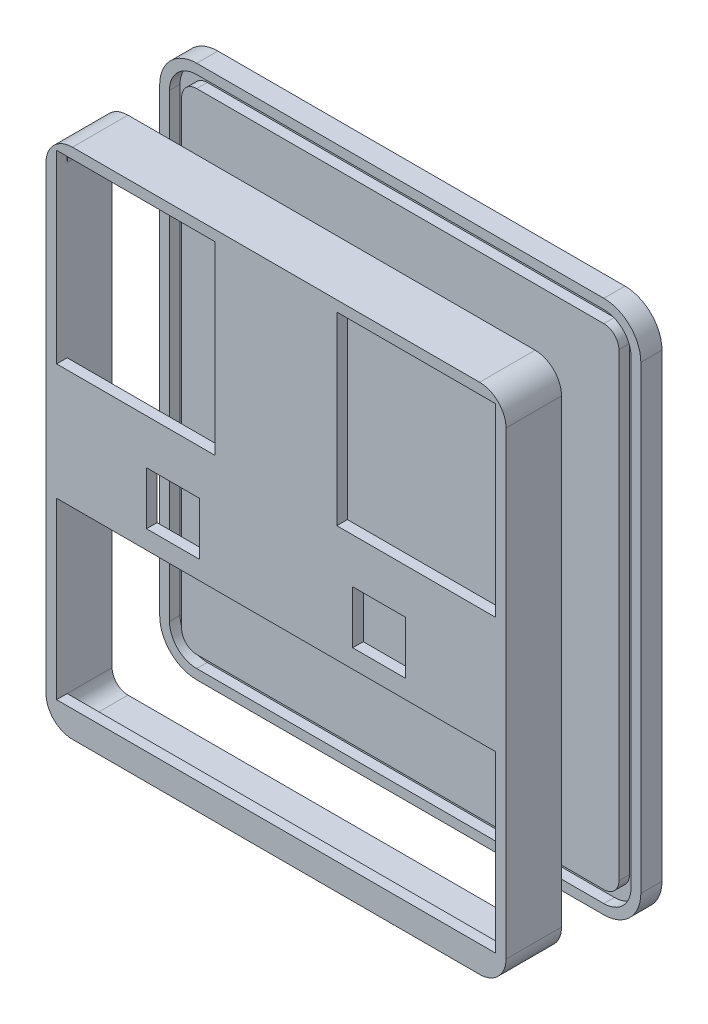
SolidWorks part; units mm, degrees
ref_plane "Front Plane" through (0, 0, 0) normal (0, 0, 1) x (1, 0, 0)
ref_plane "Top Plane" through (0, 0, 0) normal (0, 1, 0) x (1, 0, 0)
ref_plane "Right Plane" through (0, 0, 0) normal (1, 0, 0) x (0, 0, -1)
sketch "Sketch1" plane through (0, 0, 0) normal (0, 0, 1) x (1, 0, 0)
  line L1 (-43.5, -48.5) -> (43.5, -48.5)
  line L2 (-43.5, -48.5) -> (-43.5, 48.5)
  line L3 (-43.5, 48.5) -> (43.5, 48.5)
  line L4 (43.5, -48.5) -> (43.5, 48.5)
  line L5 (-43.5, -48.5) -> (43.5, 48.5) construction
  line L6 (-43.5, 48.5) -> (43.5, -48.5) construction
  point P0 (0, 0)
  dimension "D1" = 87
  dimension "D2" = 97
extrude "Boss-Extrude1" add sketch "Sketch1" along normal blind 8.5
fillet "Fillet1" radius 5 4 edges at (43.5, -48.5, 4.25) (-43.5, -48.5, 4.25) (-43.5, 48.5, 4.25) (43.5, 48.5, 4.25)
shell "Shell1" thickness 2 removed face at (0, 0, 0)
sketch "Sketch2" plane through (0, 0, 6.5) normal (0, 0, -1) x (-1, 0, 0)
  line L0 (-41.5, 0) -> (41.5, 0) construction
  line L1 (-41.5, -43.5) -> (-41.5, 43.5) construction
  line L2 (41.5, 43.5) -> (41.5, -43.5) construction
  line L3 (-38.5, 46.5) -> (38.5, 46.5) construction
  line L4 (11.5, 46.5) -> (41.5, 46.5)
  line L5 (11.5, 46.5) -> (11.5, 11.5)
  line L6 (11.5, 11.5) -> (41.5, 11.5)
  line L7 (41.5, 46.5) -> (41.5, 11.5)
  line L8 (41.5, 43.5) -> (41.5, -43.5) construction
  line L9 (-38.5, 46.5) -> (38.5, 46.5) construction
  line L10 (-11.5, 46.5) -> (-41.5, 46.5)
  line L11 (-11.5, 46.5) -> (-11.5, 11.5)
  line L12 (-11.5, 11.5) -> (-41.5, 11.5)
  line L13 (-41.5, 46.5) -> (-41.5, 11.5)
  line L14 (-41.5, -43.5) -> (-41.5, 43.5) construction
  line L16 (-24.5, 3) -> (-14.5, 3)
  line L17 (-24.5, 3) -> (-24.5, -7)
  line L18 (-24.5, -7) -> (-14.5, -7)
  line L19 (-14.5, 3) -> (-14.5, -7)
  line L20 (14.5, 3) -> (24.5, 3)
  line L21 (14.5, 3) -> (14.5, -7)
  line L22 (14.5, -7) -> (24.5, -7)
  line L23 (24.5, 3) -> (24.5, -7)
  line L24 (-41.5, -10.5) -> (41.5, -10.5)
  line L25 (-41.5, -10.5) -> (-41.5, -43.5)
  line L26 (-41.5, -43.5) -> (41.5, -43.5)
  line L27 (41.5, -10.5) -> (41.5, -43.5)
  dimension "D1" = 83
  dimension "D2" = 30
  dimension "D3" = 35
  dimension "D4" = 35
  dimension "D5" = 30
  dimension "D6" = 10
  dimension "D7" = 10
  dimension "D8" = 3
  dimension "D9" = 8.5
  dimension "D10" = 3
  dimension "D11" = 8.5
  dimension "D12" = 33
extrude "Cut-Extrude1" cut sketch "Sketch2" against normal up to next
ref_plane "Plane1" through (0, 0, -15) normal (0, 0, -1) x (-1, 0, 0)
sketch "Sketch3" plane through (0, 0, -15) normal (0, 0, -1) x (-1, 0, 0)
  line L8 (-45.5, 43.5) -> (-45.5, -43.5)
  line L9 (-38.5, -50.5) -> (38.5, -50.5)
  line L10 (45.5, -43.5) -> (45.5, 43.5)
  line L11 (38.5, 50.5) -> (-38.5, 50.5)
  line L12 (-45.5, 43.5) -> (-45.5, -43.5)
  line L13 (-38.5, -50.5) -> (38.5, -50.5)
  line L14 (45.5, -43.5) -> (45.5, 43.5)
  line L15 (38.5, 50.5) -> (-38.5, 50.5)
  arc A8 (-45.5, -43.5) -> (-38.5, -50.5) centre (-38.5, -43.5) ccw
  arc A9 (38.5, -50.5) -> (45.5, -43.5) centre (38.5, -43.5) ccw
  arc A10 (45.5, 43.5) -> (38.5, 50.5) centre (38.5, 43.5) ccw
  arc A11 (-38.5, 50.5) -> (-45.5, 43.5) centre (-38.5, 43.5) ccw
  arc A12 (-45.5, -43.5) -> (-38.5, -50.5) centre (-38.5, -43.5) ccw
  arc A13 (38.5, -50.5) -> (45.5, -43.5) centre (38.5, -43.5) ccw
  arc A14 (45.5, 43.5) -> (38.5, 50.5) centre (38.5, 43.5) ccw
  arc A15 (-38.5, 50.5) -> (-45.5, 43.5) centre (-38.5, 43.5) ccw
  dimension "D1" = 2
extrude "Boss-Extrude2" add sketch "Sketch3" along normal blind 4 separate body
sketch "Sketch4" plane through (0, 0, -15) normal (0, 0, 1) x (1, 0, 0)
  line L0 (38.5, 48.65) -> (-38.5, 48.65)
  line L1 (-43.65, 43.5) -> (-43.65, -43.5)
  line L2 (-38.5, -48.65) -> (38.5, -48.65)
  line L3 (43.65, -43.5) -> (43.65, 43.5)
  line L4 (43.5, -43.5) -> (43.5, 43.5)
  line L5 (-38.5, -48.5) -> (38.5, -48.5)
  line L6 (-43.5, 43.5) -> (-43.5, -43.5)
  line L7 (38.5, 48.5) -> (-38.5, 48.5)
  line L8 (43.5, -43.5) -> (43.5, 43.5) construction
  line L9 (-38.5, -48.5) -> (38.5, -48.5) construction
  line L10 (-43.5, 43.5) -> (-43.5, -43.5) construction
  line L11 (38.5, 48.5) -> (-38.5, 48.5) construction
  line L12 (38.5, 46.35) -> (-38.5, 46.35)
  line L13 (-41.35, 43.5) -> (-41.35, -43.5)
  line L14 (-38.5, -46.35) -> (38.5, -46.35)
  line L15 (41.35, -43.5) -> (41.35, 43.5)
  arc A0 (-38.5, 48.65) -> (-43.65, 43.5) centre (-38.5, 43.5) ccw
  arc A1 (-43.65, -43.5) -> (-38.5, -48.65) centre (-38.5, -43.5) ccw
  arc A2 (38.5, -48.65) -> (43.65, -43.5) centre (38.5, -43.5) ccw
  arc A3 (43.65, 43.5) -> (38.5, 48.65) centre (38.5, 43.5) ccw
  arc A4 (38.5, -48.5) -> (43.5, -43.5) centre (38.5, -43.5) ccw
  arc A5 (-43.5, -43.5) -> (-38.5, -48.5) centre (-38.5, -43.5) ccw
  arc A6 (-38.5, 48.5) -> (-43.5, 43.5) centre (-38.5, 43.5) ccw
  arc A7 (43.5, 43.5) -> (38.5, 48.5) centre (38.5, 43.5) ccw
  arc A8 (38.5, -48.5) -> (43.5, -43.5) centre (38.5, -43.5) ccw construction
  arc A9 (-43.5, -43.5) -> (-38.5, -48.5) centre (-38.5, -43.5) ccw construction
  arc A10 (-38.5, 48.5) -> (-43.5, 43.5) centre (-38.5, 43.5) ccw construction
  arc A11 (43.5, 43.5) -> (38.5, 48.5) centre (38.5, 43.5) ccw construction
  arc A12 (-38.5, 46.35) -> (-41.35, 43.5) centre (-38.5, 43.5) ccw
  arc A13 (-41.35, -43.5) -> (-38.5, -46.35) centre (-38.5, -43.5) ccw
  arc A14 (38.5, -46.35) -> (41.35, -43.5) centre (38.5, -43.5) ccw
  arc A15 (41.35, 43.5) -> (38.5, 46.35) centre (38.5, 43.5) ccw
  dimension "D1" = 0
  dimension "D2" = 0.15
  dimension "D3" = 2.15
extrude "Cut-Extrude2" cut sketch "Sketch4" against normal blind 2
sketch "Sketch5" plane through (0, 0, 0) normal (0, 0, -1) x (-1, 0, 0)
  line L4 (38.5, -46.5) -> (-38.5, -46.5) construction
  line L5 (41.5, 43.5) -> (41.5, -43.5) construction
  line L6 (-38.5, 46.5) -> (38.5, 46.5) construction
  line L7 (-41.5, -43.5) -> (-41.5, 43.5) construction
  line L8 (-43.5, 43.5) -> (-43.5, -43.5)
  line L9 (-38.5, -48.5) -> (38.5, -48.5)
  line L10 (43.5, -43.5) -> (43.5, 43.5)
  line L11 (38.5, 48.5) -> (-38.5, 48.5)
  line L12 (-43.5, 43.5) -> (-43.5, -43.5)
  line L13 (-38.5, -48.5) -> (38.5, -48.5)
  line L14 (43.5, -43.5) -> (43.5, 43.5)
  line L15 (38.5, 48.5) -> (-38.5, 48.5)
  line L16 (38.5, -46.5) -> (-38.5, -46.5)
  line L17 (41.5, 43.5) -> (41.5, -43.5)
  line L18 (-38.5, 46.5) -> (38.5, 46.5)
  line L19 (-41.5, -43.5) -> (-41.5, 43.5)
  arc A4 (-41.5, -43.5) -> (-38.5, -46.5) centre (-38.5, -43.5) ccw construction
  arc A5 (38.5, -46.5) -> (41.5, -43.5) centre (38.5, -43.5) ccw construction
  arc A6 (41.5, 43.5) -> (38.5, 46.5) centre (38.5, 43.5) ccw construction
  arc A7 (-38.5, 46.5) -> (-41.5, 43.5) centre (-38.5, 43.5) ccw construction
  arc A8 (-43.5, -43.5) -> (-38.5, -48.5) centre (-38.5, -43.5) ccw
  arc A9 (38.5, -48.5) -> (43.5, -43.5) centre (38.5, -43.5) ccw
  arc A10 (43.5, 43.5) -> (38.5, 48.5) centre (38.5, 43.5) ccw
  arc A11 (-38.5, 48.5) -> (-43.5, 43.5) centre (-38.5, 43.5) ccw
  arc A12 (-43.5, -43.5) -> (-38.5, -48.5) centre (-38.5, -43.5) ccw
  arc A13 (38.5, -48.5) -> (43.5, -43.5) centre (38.5, -43.5) ccw
  arc A14 (43.5, 43.5) -> (38.5, 48.5) centre (38.5, 43.5) ccw
  arc A15 (-38.5, 48.5) -> (-43.5, 43.5) centre (-38.5, 43.5) ccw
  arc A16 (-41.5, -43.5) -> (-38.5, -46.5) centre (-38.5, -43.5) ccw
  arc A17 (38.5, -46.5) -> (41.5, -43.5) centre (38.5, -43.5) ccw
  arc A18 (41.5, 43.5) -> (38.5, 46.5) centre (38.5, 43.5) ccw
  arc A19 (-38.5, 46.5) -> (-41.5, 43.5) centre (-38.5, 43.5) ccw
  dimension "D1" = 0
extrude "Boss-Extrude3" add sketch "Sketch5" along normal blind 2
equation "\"D4@Sketch2\"=\"D3@Sketch2\""
equation "\"D5@Sketch2\"=\"D2@Sketch2\""
equation "\"D11@Sketch2\"=\"D9@Sketch2\""
equation "\"D10@Sketch2\"=\"D8@Sketch2\""
